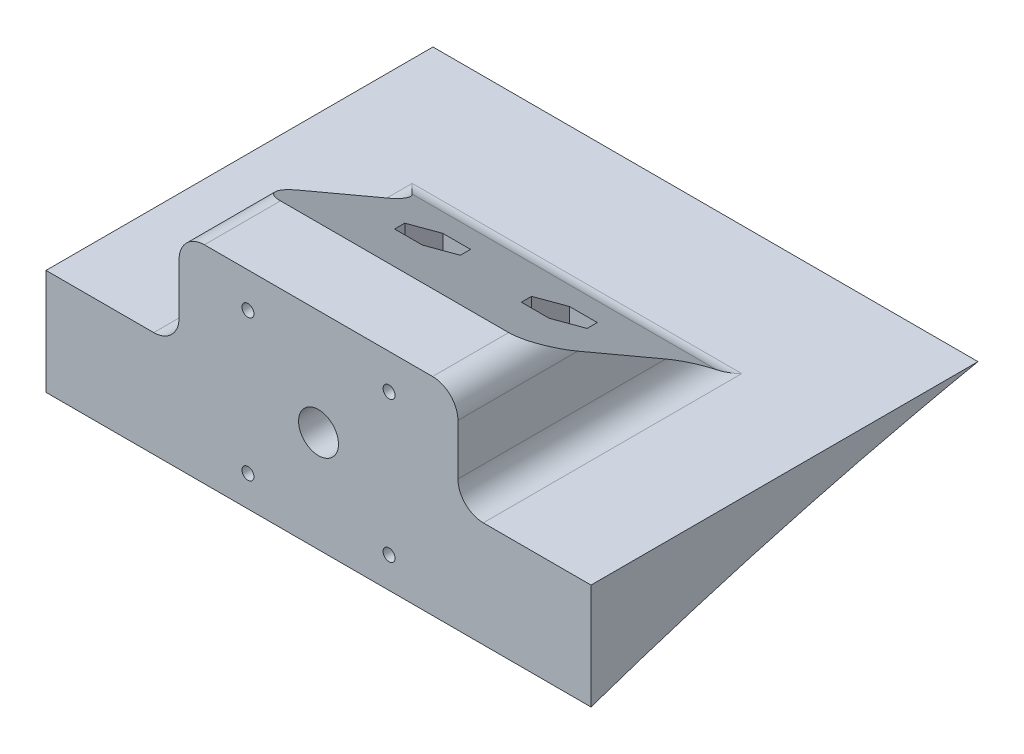
SolidWorks part; units mm, degrees
material "ABS"
ref_plane "Front Plane" through (0, 0, 0) normal (0, 0, 1) x (1, 0, 0)
ref_plane "Top Plane" through (0, 0, 0) normal (0, 1, 0) x (1, 0, 0)
ref_plane "Right Plane" through (0, 0, 0) normal (1, 0, 0) x (0, 0, -1)
curve "Curve1"
  spline degree 3 poles (0, 0.0012, 1.0003) (0, 0.0015, 0.9994) (0, 0.0028, 0.9958) (0, 0.0055, 0.9879) (0, 0.0099, 0.9747) (0, 0.0159, 0.9565) (0, 0.0233, 0.9333) (0, 0.0318, 0.9054) (0, 0.0411, 0.8731) (0, 0.051, 0.8366) (0, 0.0612, 0.7964) (0, 0.0713, 0.7528) (0, 0.0811, 0.7063) (0, 0.0903, 0.6574) (0, 0.0985, 0.6067) (0, 0.1057, 0.5546) (0, 0.1115, 0.5018) (0, 0.1158, 0.4488) (0, 0.1186, 0.3959) (0, 0.1189, 0.3436) (0, 0.1164, 0.2927) (0, 0.1112, 0.2442) (0, 0.1037, 0.1988) (0, 0.0942, 0.157) (0, 0.0831, 0.1194) (0, 0.0711, 0.0865) (0, 0.0584, 0.0585) (0, 0.0457, 0.0357) (0, 0.0334, 0.0184) (0, 0.0218, 0.0064) (0, 0.0108, -0.0005) (0, -0.0003, -0.0011) (0, -0.0092, 0.0055) (0, -0.0148, 0.017) (0, -0.0185, 0.0329) (0, -0.0204, 0.0533) (0, -0.0208, 0.0781) (0, -0.0198, 0.107) (0, -0.0176, 0.1398) (0, -0.0147, 0.176) (0, -0.0111, 0.2153) (0, -0.0074, 0.2574) (0, -0.0037, 0.3019) (0, -0.0005, 0.3484) (0, 0.002, 0.397) (0, 0.0037, 0.4471) (0, 0.0055, 0.4983) (0, 0.0069, 0.5496) (0, 0.0079, 0.6006) (0, 0.0085, 0.6505) (0, 0.0086, 0.699) (0, 0.0083, 0.7455) (0, 0.0076, 0.7894) (0, 0.0065, 0.8302) (0, 0.0053, 0.8675) (0, 0.0039, 0.9007) (0, 0.0027, 0.9296) (0, 0.0013, 0.9539) (0, 0.0006, 0.9727) (0, -0.0011, 0.9872) (0, 0, 0.9944) (0, -0.002, 0.9999) (0, -0.0005, 1) (0, 0, 1) knots 0 0 0 0 0.001372 0.005465 0.012235 0.021602 0.033461 0.047671 0.064081 0.082496 0.102719 0.124527 0.147676 0.171913 0.196978 0.222597 0.248497 0.274385 0.300041 0.32569 0.350525 0.37428 0.396711 0.417577 0.436654 0.453744 0.46868 0.481329 0.491631 0.499616 0.505546 0.510185 0.514824 0.520702 0.528516 0.538466 0.550543 0.564643 0.580638 0.598345 0.617584 0.638174 0.659922 0.682632 0.706121 0.730727 0.7557 0.780732 0.805564 0.829932 0.85357 0.876213 0.89761 0.917519 0.935698 0.951943 0.966047 0.97784 0.987174 0.993932 0.998018 0.999386 1 1 1 1
sketch "Sketch1" plane through (0, 0, 0) normal (1, 0, 0) x (0, 0, -1)
  line L3 (195.725, 0) -> (-195.725, 0) construction
  line L4 (71.5374, 26.4626) -> (-25.4, 26.4626)
  line L5 (-25.4, 26.4626) -> (-25.4, 0)
  spline S1 degree 3 poles (-25.4, 0) (-25.0834, 0.108) (-23.8218, 0.5382) (-20.9978, 1.5029) (-16.3151, 3.0589) (-6.5282, 6.2519) (9.8573, 11.2778) (28.9301, 16.5496) (47.1199, 21.0862) (60.1793, 24.0716) (68.4583, 25.8283) (71.5374, 26.4626) knots 0 0 0 0 0.001372 0.005465 0.012235 0.021602 0.047671 0.082496 0.102719 0.124527 0.137416 0.137416 0.137416 0.137416
  dimension "D1" = 26.4626
  dimension "D2" = 25.4
  dimension "D3" = 96.9374
extrude "Boss-Extrude1" add sketch "Sketch1" along normal mid plane 136.525
sketch "Sketch4" plane through (0, 0, 25.4) normal (0, 0, 1) x (1, 0, 0)
  line L0 (68.2625, 26.4626) -> (-68.2625, 26.4626) construction
  line L1 (-34.925, 51.8626) -> (34.925, 51.8626)
  line L2 (-34.925, 51.8626) -> (-34.925, 26.4626)
  line L3 (-34.925, 26.4626) -> (34.925, 26.4626)
  line L4 (34.925, 51.8626) -> (34.925, 26.4626)
  point P6 (0, 26.4626)
  dimension "D1" = 25.4
  dimension "D2" = 69.85
extrude "Boss-Extrude2" add sketch "Sketch4" against normal blind 50.8
sketch "Sketch2" plane through (0, 26.4626, 0) normal (0, 1, 0) x (1, 0, 0)
  line L0 (-68.2625, 19.05) -> (68.2625, 19.05) construction
  line L1 (-68.2625, 71.5374) -> (-68.2625, -25.4) construction
  line L2 (68.2625, 71.5374) -> (68.2625, -25.4) construction
  line L3 (-15.875, 19.05) -> (-15.875, 71.5374) construction
  line L4 (68.2625, 71.5374) -> (-68.2625, 71.5374) construction
  line L5 (15.875, 19.05) -> (15.875, 71.5374) construction
  line L6 (-68.2625, -286.8403) -> (-15.875, -286.8403) construction
  line L7 (-15.875, -286.8403) -> (15.875, -286.8403) construction
  line L8 (15.875, -286.8403) -> (68.2625, -286.8403) construction
  line L9 (-34.925, -25.4) -> (-68.2625, -25.4) construction
  circle A0 centre (-15.875, 19.05) radius 3.4925
  circle A1 centre (15.875, 19.05) radius 3.4925
  dimension "D1" = 6.985
  dimension "D2" = 6.985
  dimension "D3" = 31.75
  dimension "D4" = 44.45
extrude "Cut-Extrude1" cut sketch "Sketch2" against normal through all and the other way through all
sketch "Sketch5" plane through (0, 0, 25.4) normal (0, 0, 1) x (1, 0, 0)
  line L0 (68.2625, 0) -> (-68.2625, 0) construction
  circle A0 centre (0, 25.4) radius 5
  dimension "D1" = 10
  dimension "D2" = 25.4
extrude "Cut-Extrude2" cut sketch "Sketch5" against normal blind 12.7
sketch "Sketch6" plane through (0, 0, 25.4) normal (0, 0, 1) x (1, 0, 0)
  line L0 (0, 25.4) -> (27.6134, 53.0134) construction
  line L1 (0, 25.4) -> (45.1172, 25.4) construction
  circle A0 centre (17.6777, 43.0777) radius 1.5
  dimension "D1" = 3
  dimension "D2" = 25
  dimension "D3" = 45
extrude "Cut-Extrude3" cut sketch "Sketch6" against normal blind 6.35
pattern_circular "CirPattern1" count 4 over 360 about axis through (0, 25.4, 12.7) along (0, 0, 1) of "Cut-Extrude3"
sketch "Sketch7" plane through (-34.925, 0, 0) normal (-1, 0, 0) x (0, 0, 1)
  line L0 (-25.4, 51.8626) -> (-71.5374, 26.4626)
  line L1 (-71.5374, 26.4626) -> (25.4, 26.4626) construction
  line L2 (-71.5374, 26.4626) -> (-25.4, 26.4626)
  line L3 (-25.4, 26.4626) -> (-25.4, 51.8626)
  spline S0 degree 3 poles (25.4, 0) (25.0834, 0.108) (23.8218, 0.5382) (20.9978, 1.5029) (16.3151, 3.0589) (6.5282, 6.2519) (-9.8573, 11.2778) (-28.9301, 16.5496) (-47.1199, 21.0862) (-60.1793, 24.0716) (-68.4583, 25.8283) (-71.5374, 26.4626) knots 0 0 0 0 0.001372 0.005465 0.012235 0.021602 0.047671 0.082496 0.102719 0.124527 0.137416 0.137416 0.137416 0.137416 construction
extrude "Boss-Extrude3" add sketch "Sketch7" against normal up to surface (69.85 mm away) up to face at (34.925, 39.1626, 0)
sketch "Sketch8" plane through (0, 51.8626, 0) normal (0, 1, 0) x (1, 0, 0)
  circle A0 centre (15.875, 19.05) radius 6.35
  circle A1 centre (-15.875, 19.05) radius 6.35
  dimension "D1" = 12.7
extrude "Cut-Extrude4" cut sketch "Sketch8" against normal blind 6.35
sketch "Sketch9" plane through (-34.925, 0, 0) normal (-1, 0, 0) x (0, 0, 1)
  line L1 (-71.5374, 26.4626) -> (-37.6441, 26.4626)
  line L2 (-71.5374, 26.4626) -> (-71.5374, 51.8626)
  line L3 (-71.5374, 51.8626) -> (6.35, 51.8626)
  line L5 (-25.4, 51.8626) -> (25.4, 51.8626) construction
  line L6 (-37.6441, 26.4626) -> (6.35, 51.8626)
  line L7 (25.4, 51.8626) -> (25.4, 26.4626) construction
  dimension "D1" = 19.05
  dimension "D2" = 30
extrude "Cut-Extrude5" cut sketch "Sketch9" against normal through all both and the other way through all
sketch "Sketch10" plane through (0, 51.8626, 0) normal (0, 1, 0) x (1, 0, 0)
  line L1 (22.8407, 19.05) -> (19.3579, 25.0825)
  line L2 (19.3579, 25.0825) -> (12.3921, 25.0825)
  line L3 (12.3921, 25.0825) -> (8.9093, 19.05)
  line L4 (8.9093, 19.05) -> (12.3921, 13.0175)
  line L5 (12.3921, 13.0175) -> (19.3579, 13.0175)
  line L6 (19.3579, 13.0175) -> (22.8407, 19.05)
  line L7 (-8.9093, 19.05) -> (-12.3921, 25.0825)
  line L8 (-12.3921, 25.0825) -> (-19.3579, 25.0825)
  line L9 (-19.3579, 25.0825) -> (-22.8407, 19.05)
  line L10 (-22.8407, 19.05) -> (-19.3579, 13.0175)
  line L11 (-19.3579, 13.0175) -> (-12.3921, 13.0175)
  line L12 (-12.3921, 13.0175) -> (-8.9093, 19.05)
  circle A2 centre (15.875, 19.05) radius 6.0325 construction
  circle A3 centre (-15.875, 19.05) radius 6.0325 construction
  dimension "D1" = 12.065
  dimension "D2" = 12.065
extrude "Cut-Extrude6" cut sketch "Sketch10" against normal blind 29.21
fillet "Fillet1" radius 6.35 3 edges at (-34.925, 26.4626, -6.122) (34.925, 26.4626, -6.122) (0, 26.4626, -37.6441)
fillet "Fillet2" radius 6.35 2 edges at (-34.925, 51.8626, 15.875) (34.925, 51.8626, 15.875)
